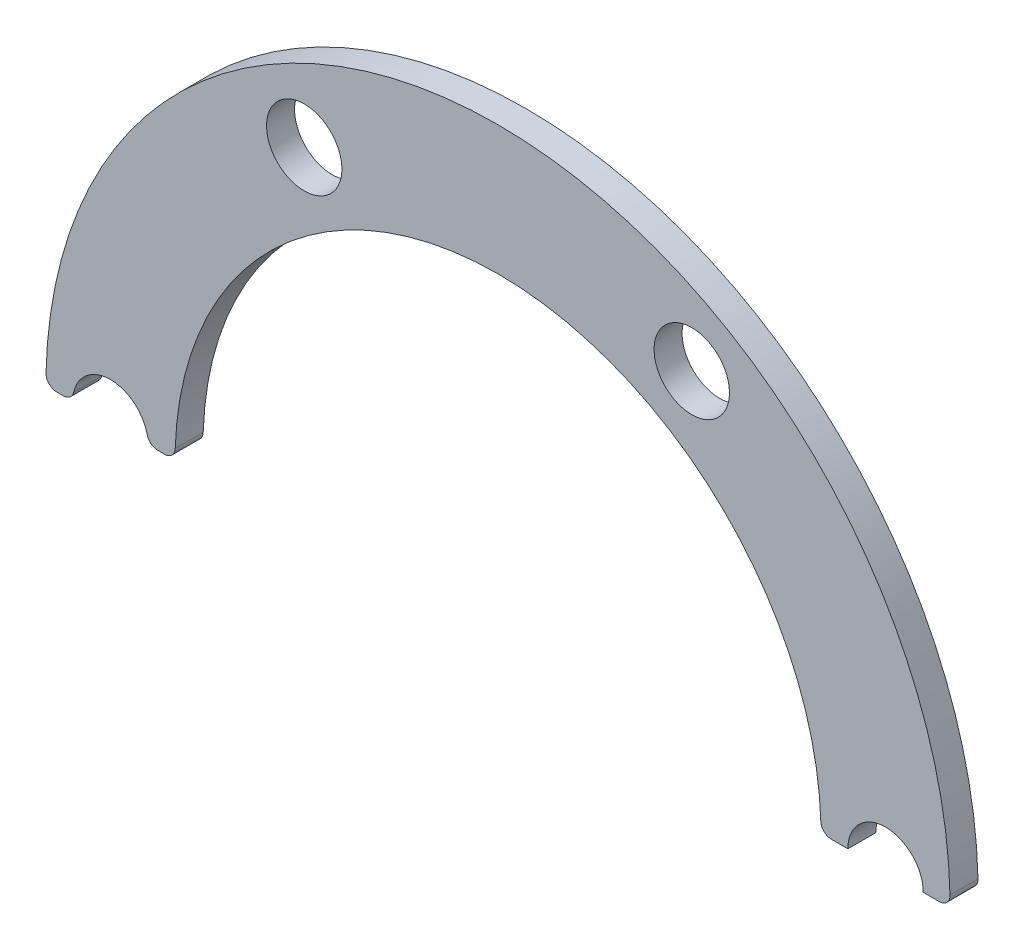
SolidWorks part; units mm, degrees
ref_plane "Alzado" through (0, 0, 0) normal (0, 0, 1) x (1, 0, 0)
ref_plane "Planta" through (0, 0, 0) normal (0, 1, 0) x (1, 0, 0)
ref_plane "Vista lateral" through (0, 0, 0) normal (1, 0, 0) x (0, 0, -1)
sketch "Croquis1" plane through (0, 0, 0) normal (0, 0, 1) x (1, 0, 0)
  line L0 (-38.1, 0) -> (-53.34, 0)
  line L2 (38.1, 0) -> (53.34, 0)
  arc A0 (53.34, 0) -> (-53.34, 0) centre (0, 0) ccw
  arc A1 (45.72, 0) -> (-45.72, 0) centre (0, 0) ccw construction
  arc A3 (38.1, 0) -> (-38.1, 0) centre (0, 0) ccw
  dimension "D1" = 91.44
  dimension "D2" = 106.68
  dimension "D3" = 76.2
extrude "Saliente-Extruir1" add sketch "Croquis1" along normal blind 3.302
sketch "Croquis2" plane through (0, 0, 3.302) normal (0, 0, 1) x (1, 0, 0)
  line L0 (-53.34, 0) -> (-38.1, 0) construction
  circle A0 centre (-45.72, 0) radius 4.445
  arc A1 (45.72, 0) -> (-45.72, 0) centre (0, 0) ccw construction
  dimension "D1" = 8.89
extrude "Cortar-Extruir1" cut sketch "Croquis2" against normal blind 3.302
ref_axis "Eje1" through (0, 0, 3.302) along (0, 0, -1)
pattern_circular "MatrizC1" count 4 every 60 about axis through (0, 0, 3.302) along (0, 0, -1) of "Cortar-Extruir1"
fillet "Redondeo1" radius 1.27 6 edges at (53.34, 0, 1.651) (38.1, 0, 1.651) (-41.275, 0, 1.651) (-50.165, 0, 1.651) (-38.1, 0, 1.651) (-53.34, 0, 1.651)
